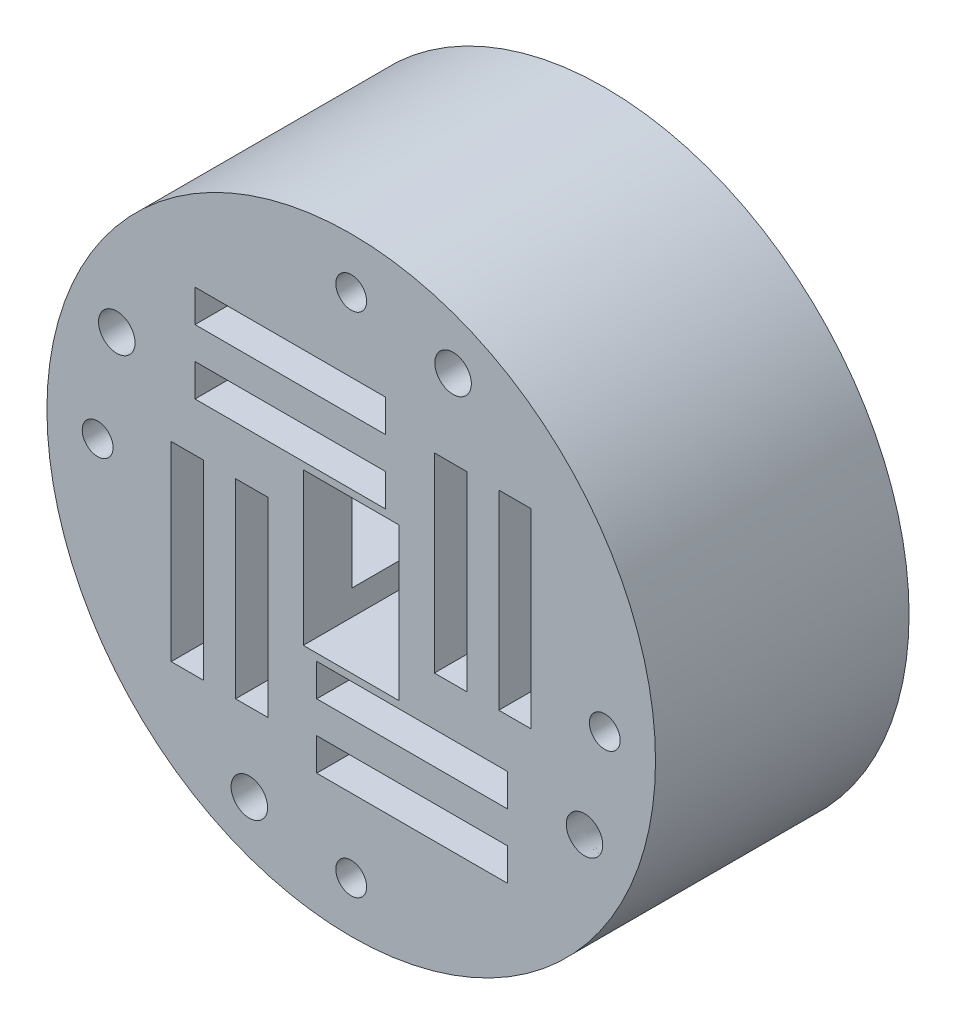
SolidWorks part; units mm, degrees
material "ABS"
ref_plane "Front Plane" through (0, 0, 0) normal (0, 0, 1) x (1, 0, 0)
ref_plane "Top Plane" through (0, 0, 0) normal (0, 1, 0) x (1, 0, 0)
ref_plane "Right Plane" through (0, 0, 0) normal (1, 0, 0) x (0, 0, -1)
sketch "Sketch1" plane through (0, 0, 0) normal (0, 0, 1) x (1, 0, 0)
  circle A0 centre (0, 0) radius 34.29
  circle A1 centre (0, 0) radius 38.1
  dimension "D1" = 76.2
  dimension "D2" = 3.81
extrude "Boss-Extrude1" add sketch "Sketch1" along normal blind 31.75
sketch "Sketch2" plane through (0, 0, 31.75) normal (0, 0, 1) x (1, 0, 0)
  circle A0 centre (0, 0) radius 38.1
  dimension "D1" = 76.2
extrude "Boss-Extrude2" add sketch "Sketch2" against normal blind 21.336
sketch "Sketch3" plane through (0, 0, 31.75) normal (0, 0, 1) x (1, 0, 0)
  line L1 (-6, -9.525) -> (6, -9.525)
  line L2 (-6, -9.525) -> (-6, 9.525)
  line L3 (-6, 9.525) -> (6, 9.525)
  line L4 (6, -9.525) -> (6, 9.525)
  line L5 (-6, -9.525) -> (6, 9.525) construction
  line L6 (-6, 9.525) -> (6, -9.525) construction
  point P0 (0, 0)
  dimension "D1" = 12
  dimension "D2" = 19.05
extrude "Cut-Extrude1" cut sketch "Sketch3" against normal up to surface (21.336 mm away) up to face at (34.29, 0, 10.414)
sketch "Sketch4" plane through (0, 0, 31.75) normal (0, 0, 1) x (1, 0, 0)
  line L1 (10.414, 19.558) -> (14.478, 19.558)
  line L2 (10.414, 19.558) -> (10.414, -4.318)
  line L3 (10.414, -4.318) -> (14.478, -4.318)
  line L4 (14.478, 19.558) -> (14.478, -4.318)
  line L5 (18.478, 19.558) -> (22.542, 19.558)
  line L6 (18.478, 19.558) -> (18.478, -4.318)
  line L7 (18.478, -4.318) -> (22.542, -4.318)
  line L8 (22.542, 19.558) -> (22.542, -4.318)
  line L56 (19.558, -10.414) -> (-4.318, -10.414)
  line L57 (19.558, -10.414) -> (19.558, -14.478)
  line L58 (19.558, -14.478) -> (-4.318, -14.478)
  line L59 (-4.318, -10.414) -> (-4.318, -14.478)
  line L60 (19.558, -18.478) -> (-4.318, -18.478)
  line L61 (19.558, -18.478) -> (19.558, -22.542)
  line L62 (19.558, -22.542) -> (-4.318, -22.542)
  line L63 (-4.318, -18.478) -> (-4.318, -22.542)
  line L64 (-10.414, -19.558) -> (-10.414, 4.318)
  line L65 (-10.414, -19.558) -> (-14.478, -19.558)
  line L66 (-14.478, -19.558) -> (-14.478, 4.318)
  line L67 (-10.414, 4.318) -> (-14.478, 4.318)
  line L68 (-18.478, -19.558) -> (-18.478, 4.318)
  line L69 (-18.478, -19.558) -> (-22.542, -19.558)
  line L70 (-22.542, -19.558) -> (-22.542, 4.318)
  line L71 (-18.478, 4.318) -> (-22.542, 4.318)
  line L72 (-19.558, 10.414) -> (4.318, 10.414)
  line L73 (-19.558, 10.414) -> (-19.558, 14.478)
  line L74 (-19.558, 14.478) -> (4.318, 14.478)
  line L75 (4.318, 10.414) -> (4.318, 14.478)
  line L76 (-19.558, 18.478) -> (4.318, 18.478)
  line L77 (-19.558, 18.478) -> (-19.558, 22.542)
  line L78 (-19.558, 22.542) -> (4.318, 22.542)
  line L79 (4.318, 18.478) -> (4.318, 22.542)
  point P36 (0, 0)
  point P37 (0, 0)
  dimension "D6" = 4
  dimension "D1" = 4.064
  dimension "D2" = 4
  dimension "D3" = 23.876
  dimension "D4" = 4.318
  dimension "D5" = 14.478
extrude "Cut-Extrude2" cut sketch "Sketch4" against normal blind 7.62
sketch "Sketch5" plane through (0, 0, 10.414) normal (0, 0, -1) x (-1, 0, 0)
  line L1 (-12.7, -6.35) -> (31.75, -6.35)
  line L2 (-12.7, -6.35) -> (-12.7, 6.35)
  line L3 (-12.7, 6.35) -> (31.75, 6.35)
  line L4 (31.75, -6.35) -> (31.75, 6.35)
  point P0 (0, 0)
  dimension "D1" = 12.7
  dimension "D2" = 31.75
  dimension "D3" = 6.35
  dimension "D4" = 12.7
extrude "Cut-Extrude3" cut sketch "Sketch5" against normal blind 15.24
sketch "Sketch6" plane through (0, 0, 10.414) normal (0, 0, -1) x (-1, 0, 0)
  line L0 (2.1029, 22.81) -> (25.6029, 22.81)
  line L1 (25.6029, 22.81) -> (25.6029, 9.96)
  line L2 (25.6029, 9.96) -> (28.6029, 9.96)
  line L3 (28.6029, 9.96) -> (28.6029, 8.96)
  line L4 (28.6029, 8.96) -> (25.6029, 8.96)
  line L5 (25.6029, 8.96) -> (25.6029, 6.35)
  line L6 (31.75, 6.35) -> (6, 6.35) construction
  line L7 (25.6029, 6.35) -> (31.75, 6.35)
  line L8 (31.75, 6.35) -> (31.75, -6.35)
  line L9 (31.75, -6.35) -> (-12.7, -6.35)
  line L10 (-12.7, -6.35) -> (-12.7, 6.35)
  line L11 (-12.7, 6.35) -> (2.1029, 6.35)
  line L12 (2.1029, 6.35) -> (2.1029, 8.96)
  line L13 (2.1029, 8.96) -> (-0.8971, 8.96)
  line L14 (-0.8971, 8.96) -> (-0.8971, 9.96)
  line L15 (-0.8971, 9.96) -> (2.1029, 9.96)
  line L16 (2.1029, 9.96) -> (2.1029, 22.81)
  line L17 (2.1029, 6.35) -> (2.1029, 3.81) construction
  line L18 (2.1029, 3.81) -> (25.6029, 3.81) construction
  line L19 (25.6029, 3.81) -> (25.6029, 6.35) construction
  circle A2 centre (0, 0) radius 38.1
  circle A3 centre (0, 0) radius 38.1 construction
  circle A4 centre (0, 0) radius 34.29 construction
  point P29 (25.7425, 22.6524)
  point P33 (0, 0)
  dimension "D1" = 19
  dimension "D2" = 23.5
  dimension "D3" = 29.5
  dimension "D4" = 5.15
  dimension "D5" = 2.54
  dimension "D6" = 1
extrude "Boss-Extrude3" add sketch "Sketch6" along normal blind 8
sketch "Sketch7" plane through (0, 0, 10.414) normal (0, 0, 1) x (1, 0, 0)
  line L1 (-6, -9.525) -> (6, -9.525)
  line L2 (-6, -9.525) -> (-6, 9.525)
  line L3 (-6, 9.525) -> (6, 9.525)
  line L4 (6, -9.525) -> (6, 9.525)
extrude "Boss-Extrude4" add sketch "Sketch7" along normal blind 2.54
sketch "Sketch8" plane through (0, 0, 2.414) normal (0, 0, -1) x (-1, 0, 0)
  line L1 (28.6029, 9.96) -> (25.6029, 9.96) construction
  circle A0 centre (29.3529, 12.754) radius 2.286
  circle A1 centre (0, 0) radius 34.29 construction
  circle A5 centre (12.754, -29.3529) radius 2.286
  circle A7 centre (-12.754, 29.3529) radius 2.286
  circle A8 centre (-29.3529, -12.754) radius 2.286 [skipped]
  point P15 (0, 0)
  dimension "D1" = 4.572
  dimension "D2" = 2.794
  dimension "D3" = 4
extrude "Cut-Extrude4" cut sketch "Sketch8" against normal through all
chamfer "Chamfer1" distance 1.905 angle 45 1 edges at (34.29, 0, 0)
sketch "Sketch9" plane through (0, 0, 2.414) normal (0, 0, -1) x (-1, 0, 0)
  circle A0 centre (0, -31.75) radius 1.9304
  circle A1 centre (-31.75, 0) radius 1.9304
  circle A2 centre (0, 31.75) radius 1.9304
  circle A3 centre (31.75, 0) radius 1.9304
  point P4 (-3.2022, 3.7526)
  point P5 (0, 0)
  point P9 (0, 0)
  dimension "D1" = 3.8608
  dimension "D2" = 31.75
  dimension "D3" = 4
extrude "Cut-Extrude5" cut sketch "Sketch9" against normal through all
sketch "Sketch10" plane through (0, 0, 31.75) normal (0, 0, 1) x (1, 0, 0)
  line L0 (-4.318, -14.478) -> (19.558, -14.478) construction
  circle A0 centre (29.21, -12.446) radius 2.286
  dimension "D3" = 4.572
  dimension "D1" = 2.032
  dimension "D2" = 9.652
sketch3d "3DSketch1"
  spline S1 degree 3 poles (29.21, -12.446, 31.75) (28.042, -13.6065, 25.0786) (25.3651, -15.5316, 21.1462) (18.6134, -22.0102, 16.5039) (14.8693, -23.1531, 15.3723) (10.0157, -25.2815, 10.4751) (8.0896, -27.4395, 0) knots 0 0 0 0 0.447008 0.522827 0.758186 1 1 1 1
  point P1 (18.5984, -25.6164, 20.1502)
  point P3 (5.1984, -6.35, 2.414)
  point P5 (13.3453, -28.7186, 11.2533)
  point P6 (0, 0, 0)
  point P7 (18.5984, -24.2971, 20.9373)
  point P9 (13.1038, -28.365, 2.414)
  point P11 (17.1478, -23.515, 10.6529)
  point P12 (8.8008, -29.5658, 2.414)
  point P13 (18.7986, -21.5137, 22.6519)
  point P14 (13.3453, -26.9173, 10.6529)
  point P15 (18.5984, -23.415, 22.6519)
  point P16 (-18.9551, -30.8347, 0)
  point P17 (8.0896, -27.4395, 0)
  point P18 (11.4121, -29.715, 18.5597)
  point P19 (11.4121, -27.3953, 18.9464)
  point P20 (0, 0, 0)
  point P21 (0, 0, 0)
  point P22 (18.5984, -22.1596, 24.1682)
  point P23 (18.2532, -21.2958, 22.2608)
  point P24 (10.9865, -26.8343, 17.5511)
  point P25 (17.9187, -21.188, 21.7963)
  point P26 (21.4312, -19.0168, 21.1494)
  point P27 (13.2334, -24.7239, 14.652)
  point P28 (14.5182, -23.4177, 14.4316)
  point P29 (20.7421, -19.9451, 17.9829)
sweep "Cut-Sweep1" cut profiles "Sketch10" path "3DSketch1"
sketch "Sketch14" plane through (0, 0, 2.414) normal (0, 0, -1) x (-1, 0, 0)
  line L1 (-27.94, -15.113) -> (-20.32, -15.113)
  line L2 (-27.94, -15.113) -> (-27.94, 15.113)
  line L3 (-27.94, 15.113) -> (-20.32, 15.113)
  line L4 (-20.32, -15.113) -> (-20.32, 15.113)
  line L5 (-27.94, -15.113) -> (-20.32, 15.113) construction
  line L6 (-27.94, 15.113) -> (-20.32, -15.113) construction
  circle A0 centre (-31.75, 0) radius 1.9304 construction
  point P0 (-24.13, 0)
  point P5 (-24.7168, 0)
  point P6 (0, 0)
  dimension "D3" = 3.81
  dimension "D1" = 7.62
  dimension "D2" = 30.226
extrude "Cut-Extrude6" cut sketch "Sketch14" against normal blind 8.89
